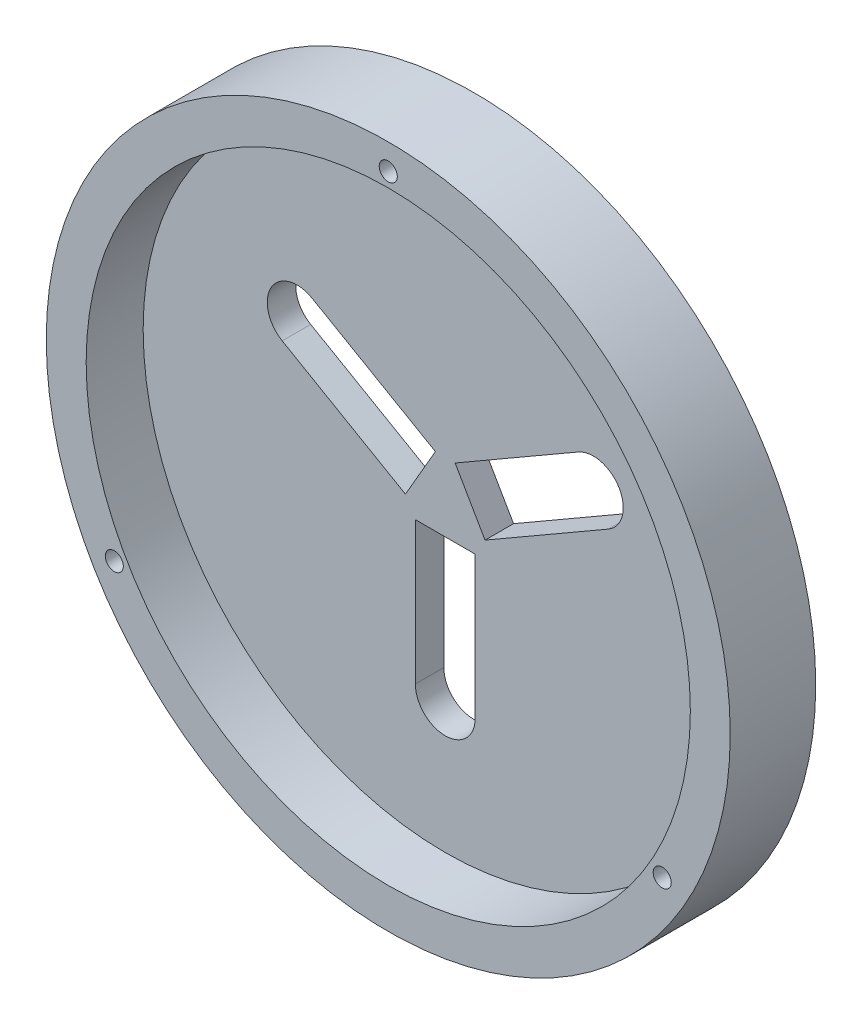
SolidWorks part; units mm, degrees
ref_plane "Alzado" through (0, 0, 0) normal (0, 0, 1) x (1, 0, 0)
ref_plane "Planta" through (0, 0, 0) normal (0, 1, 0) x (1, 0, 0)
ref_plane "Vista lateral" through (0, 0, 0) normal (1, 0, 0) x (0, 0, -1)
sketch "Croquis1" plane through (0, 0, 0) normal (0, 0, 1) x (1, 0, 0)
  circle A0 centre (0, 0) radius 55
  dimension "D1" = 110
extrude "Disco" add sketch "Croquis1" along normal blind 5
sketch "Croquis6" plane through (0, 0, 5) normal (0, 0, 1) x (1, 0, 0)
  line L0 (-5.25, 0) -> (-5.25, -30)
  line L1 (5.25, 0) -> (5.25, -30)
  line L2 (2.625, 4.5466) -> (-23.3558, 19.5466)
  line L3 (-2.625, -4.5466) -> (-28.6058, 10.4534)
  line L4 (2.625, -4.5466) -> (28.6058, 10.4534)
  line L5 (-2.625, 4.5466) -> (23.3558, 19.5466)
  arc A1 (-5.25, 0) -> (5.25, 0) centre (0, 0) cw
  arc A2 (-5.25, -30) -> (5.25, -30) centre (0, -30) ccw
  arc A3 (2.625, 4.5466) -> (-2.625, -4.5466) centre (0, 0) cw
  arc A4 (-23.3558, 19.5466) -> (-28.6058, 10.4534) centre (-25.9808, 15) ccw
  arc A5 (2.625, -4.5466) -> (-2.625, 4.5466) centre (0, 0) cw
  arc A6 (28.6058, 10.4534) -> (23.3558, 19.5466) centre (25.9808, 15) ccw
  point P22 (0, 0)
  dimension "D1" = 30
  dimension "D3" = 5.25
  dimension "D2" = 3
extrude "Cortar-Extruir1" cut sketch "Croquis6" against normal blind 10 contours L2 A4 L3 A3 | L5 A6 L4 A5 | L1 A2 L0 A1
sketch "Croquis7" plane through (0, 0, 5) normal (0, 0, 1) x (1, 0, 0)
  circle A0 centre (0, 0) radius 53
  circle A1 centre (0, 0) radius 60
  circle A2 centre (0, 0) radius 53
  circle M3 centre (0, 0) radius 55
  dimension "D1" = 120
  dimension "D2" = 106
extrude "Saliente-Extruir1" add sketch "Croquis7" along normal blind 10 and the other way through all contours A0 M3 | A1 M3 region at (-58.3029, 0, 5) region at (-53.4444, 0, 5)
sketch "Croquis8" plane through (0, 0, 5) normal (0, 0, 1) x (1, 0, 0)
  line L3 (-8.7141, -5.0311) -> (0, 10.0622)
  line L4 (0, 10.0622) -> (8.7141, -5.0311)
  line L5 (8.7141, -5.0311) -> (-8.7141, -5.0311)
extrude "Saliente-Extruir6" add sketch "Croquis8" against normal blind 5
sketch "Croquis9" plane through (0, 0, 15) normal (0, 0, 1) x (1, 0, 0)
  line L0 (0, 0) -> (0, 55.5) construction
  circle A0 centre (0, 55.5) radius 1.5875
  circle A1 centre (48.0644, -27.75) radius 1.5875
  circle A2 centre (-48.0644, -27.75) radius 1.5875
  point P12 (0, 0)
  dimension "D1" = 3
  dimension "D2" = 55.5
extrude "Cortar-Extruir2" cut sketch "Croquis9" against normal through all
sketch "Croquis10" plane through (0, 0, 0) normal (0, 0, -1) x (-1, 0, 0)
  line L0 (0, 0) -> (0, 55.5) construction
  circle A0 centre (0, 55.5) radius 3
  circle A1 centre (48.0644, -27.75) radius 3
  circle A2 centre (-48.0644, -27.75) radius 3
  point P11 (0, 0)
  dimension "D1" = 6
  dimension "D2" = 3
extrude "Cortar-Extruir3" cut sketch "Croquis10" against normal blind 3
